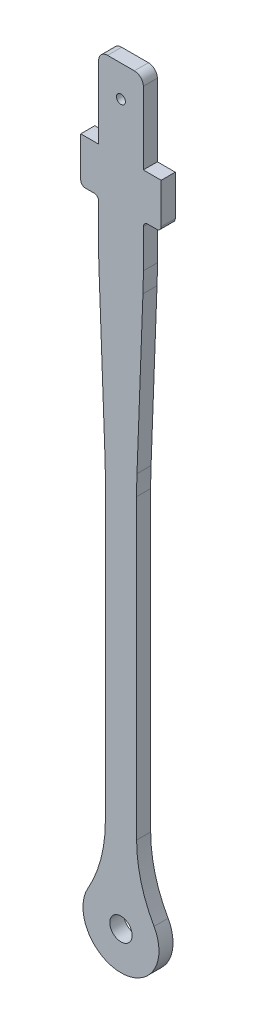
SolidWorks part; units mm, degrees
material "Hexcel AS4C (3000 Filaments)"
ref_plane "Front Plane" through (0, 0, 0) normal (0, 0, 1) x (1, 0, 0)
ref_plane "Top Plane" through (0, 0, 0) normal (0, 1, 0) x (1, 0, 0)
ref_plane "Right Plane" through (0, 0, 0) normal (1, 0, 0) x (0, 0, -1)
sketch "Sketch2" plane through (0, 0, 0) normal (0, 0, 1) x (1, 0, 0)
  line L0 (4.552, 53.6545) -> (6.243, 98.7455)
  line L1 (-4.445, -50.8) -> (4.445, -50.8) construction
  line L2 (-4.445, -36.5408) -> (-4.445, 47.9435)
  line L3 (-4.445, 50.8) -> (4.445, 50.8) construction
  line L4 (4.445, -36.5408) -> (4.445, 47.9435)
  line L5 (-4.445, -50.8) -> (4.445, 50.8) construction
  line L6 (-4.445, 50.8) -> (4.445, -50.8) construction
  line L7 (6.35, 104.4565) -> (6.35, 149.86) construction
  line L8 (3.81, 152.4) -> (-3.81, 152.4)
  line L9 (-6.35, 149.86) -> (-6.35, 104.4565) construction
  line L10 (-6.243, 98.7455) -> (-4.552, 53.6545)
  line L11 (-6.35, 149.86) -> (-6.35, 129.286)
  line L12 (-6.35, 129.286) -> (-11.43, 129.286)
  line L13 (-11.43, 129.286) -> (-11.43, 117.856)
  line L14 (-10.16, 116.586) -> (-7.62, 116.586)
  line L15 (-6.35, 115.316) -> (-6.35, 104.4565)
  line L16 (6.35, 104.4565) -> (6.35, 115.316)
  line L17 (7.62, 116.586) -> (10.16, 116.586)
  line L18 (11.43, 117.856) -> (11.43, 129.286)
  line L19 (11.43, 129.286) -> (6.35, 129.286)
  line L20 (6.35, 129.286) -> (6.35, 149.86)
  circle A0 centre (0, 143.51) radius 1.27
  arc A1 (-9.3931, -55.3174) -> (9.3931, -55.3174) centre (0, -60.6374) ccw
  circle A2 centre (0, -60.6374) radius 3.175
  arc A3 (9.3931, -55.3174) -> (4.445, -36.5408) centre (42.545, -36.5408) cw
  arc A4 (-9.3931, -55.3174) -> (-4.445, -36.5408) centre (-42.545, -36.5408) ccw
  arc A5 (6.35, 149.86) -> (3.81, 152.4) centre (3.81, 149.86) ccw
  arc A6 (-3.81, 152.4) -> (-6.35, 149.86) centre (-3.81, 149.86) ccw
  arc A7 (6.243, 98.7455) -> (6.35, 104.4565) centre (-146.05, 104.4565) ccw
  arc A8 (-6.35, 104.4565) -> (-6.243, 98.7455) centre (146.05, 104.4565) ccw
  arc A9 (-4.445, 47.9435) -> (-4.552, 53.6545) centre (-156.845, 47.9435) ccw
  arc A10 (4.552, 53.6545) -> (4.445, 47.9435) centre (156.845, 47.9435) ccw
  arc A11 (10.16, 116.586) -> (11.43, 117.856) centre (10.16, 117.856) ccw
  arc A12 (6.35, 115.316) -> (7.62, 116.586) centre (7.62, 115.316) cw
  arc A13 (-7.62, 116.586) -> (-6.35, 115.316) centre (-7.62, 115.316) cw
  arc A14 (-11.43, 117.856) -> (-10.16, 116.586) centre (-10.16, 117.856) ccw
  point P0 (0, 0)
  point P14 (0, 152.4)
  point P23 (6.35, 152.4)
  point P26 (-6.35, 152.4)
  point P29 (6.35, 101.6)
  point P32 (-6.35, 101.6)
  point P42 (-11.43, 117.8992)
  point P52 (6.35, 116.586)
  point P55 (-6.35, 116.586)
  point P58 (-11.43, 116.586)
  dimension "D3" = 2.54
  dimension "D8" = 6.35
  dimension "D9" = 7.62
  dimension "D10" = 38.1
  dimension "D11" = 2.54
  dimension "D12" = 152.4
  dimension "D16" = 1.27
  dimension "D1" = 8.89
  dimension "D2" = 101.6
  dimension "D4" = 50.8
  dimension "D5" = 50.8
  dimension "D6" = 12.7
  dimension "D7" = 8.89
  dimension "D13" = 5.08
  dimension "D14" = 23.114
  dimension "D15" = 12.7
extrude "Boss-Extrude1" add sketch "Sketch2" along normal blind 4
